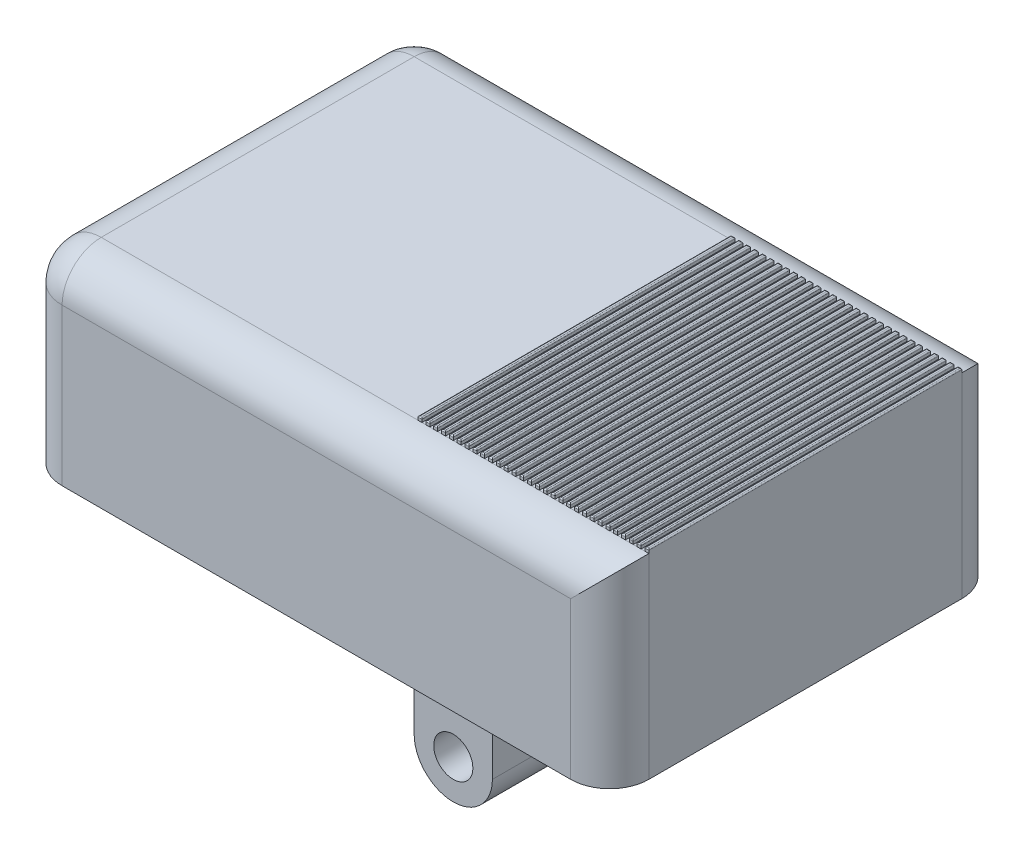
SolidWorks part; units mm, degrees
ref_plane "Front Plane" through (0, 0, 0) normal (0, 0, 1) x (1, 0, 0)
ref_plane "Top Plane" through (0, 0, 0) normal (0, 1, 0) x (1, 0, 0)
ref_plane "Right Plane" through (0, 0, 0) normal (1, 0, 0) x (0, 0, -1)
sketch "Sketch2" plane through (0, 0, 0) normal (0, 1, 0) x (1, 0, 0)
  line L1 (-37.5, -25) -> (37.5, -25)
  line L2 (-37.5, -25) -> (-37.5, 25)
  line L3 (-37.5, 25) -> (37.5, 25)
  line L4 (37.5, -25) -> (37.5, 25)
  line L5 (-37.5, -25) -> (37.5, 25) construction
  line L6 (-37.5, 25) -> (37.5, -25) construction
  point P0 (0, 0)
  dimension "D1" = 75
  dimension "D2" = 50
extrude "Boss-Extrude1" add sketch "Sketch2" along normal blind 25
sketch "Sketch3" plane through (0, 0, 0) normal (0, -1, 0) x (1, 0, 0)
  line L0 (37.5, 25) -> (37.5, -25) construction
  line L1 (7.5, -10) -> (17.5, -10)
  line L2 (7.5, -10) -> (7.5, 10)
  line L3 (7.5, 10) -> (17.5, 10)
  line L4 (17.5, -10) -> (17.5, 10)
  line L5 (7.5, -10) -> (17.5, 10) construction
  line L6 (7.5, 10) -> (17.5, -10) construction
  line L8 (7.5, 10) -> (17.5, 10)
  line L9 (7.5, 10) -> (7.5, 20)
  line L10 (7.5, 20) -> (17.5, 20)
  line L11 (17.5, 10) -> (17.5, 20)
  line L12 (7.5, -10) -> (17.5, -10)
  line L13 (7.5, -10) -> (7.5, -20)
  line L14 (7.5, -20) -> (17.5, -20)
  line L15 (17.5, -10) -> (17.5, -20)
  point P0 (12.5, 0)
  dimension "D1" = 20
  dimension "D2" = 20
  dimension "D3" = 10
  dimension "D4" = 10
  dimension "D5" = 10
extrude "Boss-Extrude2" add sketch "Sketch3" along normal blind 15 contours L15 L1 L13 L14 | L3 L11 L10 L9 region at (12.5, 0, -15) region at (12.5, 0, 15)
fillet "Fillet1" radius 5 4 edges at (17.5, -15, -15) (7.5, -15, -15) (17.5, -15, 15) (7.5, -15, 15)
sketch "Sketch4" plane through (0, 0, 20) normal (0, 0, 1) x (1, 0, 0)
  circle A0 centre (12.5, -10) radius 2.5
  dimension "D1" = 5
extrude "Cut-Extrude1" cut sketch "Sketch4" against normal through all
sketch "Sketch5" plane through (0, 0, 0) normal (0, -1, 0) x (1, 0, 0)
  line L0 (37.5, 25) -> (37.5, -25) construction
  circle A0 centre (27.5, 0) radius 2.75
  point P4 (0, 0)
  dimension "D1" = 5.5
  dimension "D2" = 10
extrude "Cut-Extrude2" cut sketch "Sketch5" against normal blind 5
sketch "Sketch6" plane through (0, 5, 0) normal (0, -1, 0) x (1, 0, 0)
  circle A0 centre (27.5, 0) radius 2.125
  dimension "D1" = 4.25
extrude "Boss-Extrude3" add sketch "Sketch6" along normal blind 10
ref_plane "Plane1" through (0, 2, 0) normal (0, -1, 0) x (-1, 0, 0)
sketch "Sketch7" plane through (0, 2, 0) normal (0, -1, 0) x (-1, 0, 0)
  line L0 (-27.5, 0) -> (-30.5, 0) construction
  line L1 (-27.5, 0) -> (-30.0981, -1.5)
  line L2 (-27.5, 0) -> (-30.0981, 1.5)
  line L3 (-27.5, 2.25) -> (-27.5, -2.25) construction
  line L4 (-27.5, 0) -> (-24.9019, 1.5)
  line L5 (-27.5, 0) -> (-24.9019, -1.5)
  circle A0 centre (-27.5, 0) radius 2.25
  circle A1 centre (-27.5, 0) radius 2.75
  point P11 (-27.5, 0)
  dimension "D1" = 4.5
  dimension "D7" = 5.5
  dimension "D2" = 3
  dimension "D3" = 3
  dimension "D4" = 3
  dimension "D5" = 30
  dimension "D6" = 30
extrude "Boss-Extrude4" add sketch "Sketch7" along normal blind 0.75 contours L2 A1 L1 A0 | L5 A1 L4 A0 region at (29.8953, 2, 0) region at (25.1047, 2, 0)
fillet "Fillet2" radius 5 7 edges at (-37.5, 12.5, -25) (0, 25, 25) (-37.5, 25, 0) (0, 25, -25) (37.5, 12.5, -25) (37.5, 12.5, 25) (-37.5, 12.5, 25)
sketch "Sketch8" plane through (0, 25, 0) normal (0, 1, 0) x (1, 0, 0)
  line L0 (37.5, 20) -> (-32.5, 20) construction
  line L1 (37.5, -20) -> (37, -20)
  line L2 (37.5, -20) -> (37.5, 20)
  line L3 (37.5, 20) -> (37, 20)
  line L4 (37, -20) -> (37, 20)
  line L5 (36.5, -20) -> (36.5, 20)
  line L6 (36.5, 20) -> (36, 20)
  line L7 (36, -20) -> (36, 20)
  line L8 (36.5, -20) -> (36, -20)
  line L9 (35.5, -20) -> (35.5, 20)
  line L10 (35.5, 20) -> (35, 20)
  line L11 (35, -20) -> (35, 20)
  line L12 (35.5, -20) -> (35, -20)
  line L13 (34.5, -20) -> (34.5, 20)
  line L14 (34.5, 20) -> (34, 20)
  line L15 (34, -20) -> (34, 20)
  line L16 (34.5, -20) -> (34, -20)
  line L17 (33.5, -20) -> (33.5, 20)
  line L18 (33.5, 20) -> (33, 20)
  line L19 (33, -20) -> (33, 20)
  line L20 (33.5, -20) -> (33, -20)
  line L21 (32.5, -20) -> (32.5, 20)
  line L22 (32.5, 20) -> (32, 20)
  line L23 (32, -20) -> (32, 20)
  line L24 (32.5, -20) -> (32, -20)
  line L25 (31.5, -20) -> (31.5, 20)
  line L26 (31.5, 20) -> (31, 20)
  line L27 (31, -20) -> (31, 20)
  line L28 (31.5, -20) -> (31, -20)
  line L29 (30.5, -20) -> (30.5, 20)
  line L30 (30.5, 20) -> (30, 20)
  line L31 (30, -20) -> (30, 20)
  line L32 (30.5, -20) -> (30, -20)
  line L33 (29.5, -20) -> (29.5, 20)
  line L34 (29.5, 20) -> (29, 20)
  line L35 (29, -20) -> (29, 20)
  line L36 (29.5, -20) -> (29, -20)
  line L37 (28.5, -20) -> (28.5, 20)
  line L38 (28.5, 20) -> (28, 20)
  line L39 (28, -20) -> (28, 20)
  line L40 (28.5, -20) -> (28, -20)
  line L41 (27.5, -20) -> (27.5, 20)
  line L42 (27.5, 20) -> (27, 20)
  line L43 (27, -20) -> (27, 20)
  line L44 (27.5, -20) -> (27, -20)
  line L45 (26.5, -20) -> (26.5, 20)
  line L46 (26.5, 20) -> (26, 20)
  line L47 (26, -20) -> (26, 20)
  line L48 (26.5, -20) -> (26, -20)
  line L49 (25.5, -20) -> (25.5, 20)
  line L50 (25.5, 20) -> (25, 20)
  line L51 (25, -20) -> (25, 20)
  line L52 (25.5, -20) -> (25, -20)
  line L53 (24.5, -20) -> (24.5, 20)
  line L54 (24.5, 20) -> (24, 20)
  line L55 (24, -20) -> (24, 20)
  line L56 (24.5, -20) -> (24, -20)
  line L57 (23.5, -20) -> (23.5, 20)
  line L58 (23.5, 20) -> (23, 20)
  line L59 (23, -20) -> (23, 20)
  line L60 (23.5, -20) -> (23, -20)
  line L61 (22.5, -20) -> (22.5, 20)
  line L62 (22.5, 20) -> (22, 20)
  line L63 (22, -20) -> (22, 20)
  line L64 (22.5, -20) -> (22, -20)
  line L65 (21.5, -20) -> (21.5, 20)
  line L66 (21.5, 20) -> (21, 20)
  line L67 (21, -20) -> (21, 20)
  line L68 (21.5, -20) -> (21, -20)
  line L69 (20.5, -20) -> (20.5, 20)
  line L70 (20.5, 20) -> (20, 20)
  line L71 (20, -20) -> (20, 20)
  line L72 (20.5, -20) -> (20, -20)
  line L73 (19.5, -20) -> (19.5, 20)
  line L74 (19.5, 20) -> (19, 20)
  line L75 (19, -20) -> (19, 20)
  line L76 (19.5, -20) -> (19, -20)
  line L77 (18.5, -20) -> (18.5, 20)
  line L78 (18.5, 20) -> (18, 20)
  line L79 (18, -20) -> (18, 20)
  line L80 (18.5, -20) -> (18, -20)
  line L81 (17.5, -20) -> (17.5, 20)
  line L82 (17.5, 20) -> (17, 20)
  line L83 (17, -20) -> (17, 20)
  line L84 (17.5, -20) -> (17, -20)
  line L85 (16.5, -20) -> (16.5, 20)
  line L86 (16.5, 20) -> (16, 20)
  line L87 (16, -20) -> (16, 20)
  line L88 (16.5, -20) -> (16, -20)
  line L89 (15.5, -20) -> (15.5, 20)
  line L90 (15.5, 20) -> (15, 20)
  line L91 (15, -20) -> (15, 20)
  line L92 (15.5, -20) -> (15, -20)
  line L93 (14.5, -20) -> (14.5, 20)
  line L94 (14.5, 20) -> (14, 20)
  line L95 (14, -20) -> (14, 20)
  line L96 (14.5, -20) -> (14, -20)
  line L97 (13.5, -20) -> (13.5, 20)
  line L98 (13.5, 20) -> (13, 20)
  line L99 (13, -20) -> (13, 20)
  line L100 (13.5, -20) -> (13, -20)
  line L101 (12.5, -20) -> (12.5, 20)
  line L102 (12.5, 20) -> (12, 20)
  line L103 (12, -20) -> (12, 20)
  line L104 (12.5, -20) -> (12, -20)
  line L105 (11.5, -20) -> (11.5, 20)
  line L106 (11.5, 20) -> (11, 20)
  line L107 (11, -20) -> (11, 20)
  line L108 (11.5, -20) -> (11, -20)
  line L109 (10.5, -20) -> (10.5, 20)
  line L110 (10.5, 20) -> (10, 20)
  line L111 (10, -20) -> (10, 20)
  line L112 (10.5, -20) -> (10, -20)
  line L113 (9.5, -20) -> (9.5, 20)
  line L114 (9.5, 20) -> (9, 20)
  line L115 (9, -20) -> (9, 20)
  line L116 (9.5, -20) -> (9, -20)
  line L117 (8.5, -20) -> (8.5, 20)
  line L118 (8.5, 20) -> (8, 20)
  line L119 (8, -20) -> (8, 20)
  line L120 (8.5, -20) -> (8, -20)
  line L121 (37.5, -20) -> (36.5, -20) construction
  dimension "D1" = 0.5
  dimension "D3" = 1
  dimension "D2" = 30
extrude "Boss-Extrude5" add sketch "Sketch8" along normal blind 0.5
fillet "Fillet3" radius 0.15 120 edges at (37.25, 25.5, 20) (37, 25.5, 0) (37.25, 25.5, -20) (37.5, 25.5, 0) (36, 25.5, 0) (36.25, 25.5, -20) (36.5, 25.5, 0) (36.25, 25.5, 20) (35, 25.5, 0) (35.25, 25.5, -20) (35.5, 25.5, 0) (35.25, 25.5, 20) (34, 25.5, 0) (34.25, 25.5, -20) (34.5, 25.5, 0) (34.25, 25.5, 20) (33, 25.5, 0) (33.25, 25.5, -20) (33.5, 25.5, 0) (33.25, 25.5, 20) (32, 25.5, 0) (32.25, 25.5, -20) (32.5, 25.5, 0) (32.25, 25.5, 20) (30, 25.5, 0) (30.25, 25.5, -20) (30.5, 25.5, 0) (30.25, 25.5, 20) (31, 25.5, 0) (31.25, 25.5, -20) (31.5, 25.5, 0) (31.25, 25.5, 20) (29, 25.5, 0) (29.25, 25.5, -20) (29.5, 25.5, 0) (29.25, 25.5, 20) (28, 25.5, 0) (28.25, 25.5, -20) (28.5, 25.5, 0) (28.25, 25.5, 20) (27, 25.5, 0) (27.25, 25.5, -20) (27.5, 25.5, 0) (27.25, 25.5, 20) (26, 25.5, 0) (26.25, 25.5, -20) (26.5, 25.5, 0) (26.25, 25.5, 20) (25, 25.5, 0) (25.25, 25.5, -20) (25.5, 25.5, 0) (25.25, 25.5, 20) (24, 25.5, 0) (24.25, 25.5, -20) (24.5, 25.5, 0) (24.25, 25.5, 20) (23, 25.5, 0) (23.25, 25.5, -20) (23.5, 25.5, 0) (23.25, 25.5, 20) (22, 25.5, 0) (22.25, 25.5, -20) (22.5, 25.5, 0) (22.25, 25.5, 20) (21, 25.5, 0) (21.25, 25.5, -20) (21.5, 25.5, 0) (21.25, 25.5, 20) (20, 25.5, 0) (20.25, 25.5, -20) (20.5, 25.5, 0) (20.25, 25.5, 20) (19, 25.5, 0) (19.25, 25.5, -20) (19.5, 25.5, 0) (19.25, 25.5, 20) (18, 25.5, 0) (18.25, 25.5, -20) (18.5, 25.5, 0) (18.25, 25.5, 20) (17, 25.5, 0) (17.25, 25.5, -20) (17.5, 25.5, 0) (17.25, 25.5, 20) (16, 25.5, 0) (16.25, 25.5, -20) (16.5, 25.5, 0) (16.25, 25.5, 20) (15, 25.5, 0) (15.25, 25.5, -20) (15.5, 25.5, 0) (15.25, 25.5, 20) (14, 25.5, 0) (14.25, 25.5, -20) (14.5, 25.5, 0) (14.25, 25.5, 20) (13, 25.5, 0) (13.25, 25.5, -20) (13.5, 25.5, 0) (13.25, 25.5, 20) (12, 25.5, 0) (12.25, 25.5, -20) (12.5, 25.5, 0) (12.25, 25.5, 20) (11, 25.5, 0) (11.25, 25.5, -20) (11.5, 25.5, 0) (11.25, 25.5, 20) (10, 25.5, 0) (10.25, 25.5, -20) (10.5, 25.5, 0) (10.25, 25.5, 20) (9, 25.5, 0) (9.25, 25.5, -20) (9.5, 25.5, 0) (9.25, 25.5, 20) (8, 25.5, 0) (8.25, 25.5, -20) (8.5, 25.5, 0) (8.25, 25.5, 20)
sketch "Sketch9" plane through (0, 0, 0) normal (0, -1, 0) x (1, 0, 0)
  line L0 (-37.5, -20) -> (-37.5, 20) construction
  line L1 (-25.5, -7.5) -> (-20.5, -7.5)
  line L2 (-25.5, -7.5) -> (-25.5, 7.5)
  line L3 (-25.5, 7.5) -> (-20.5, 7.5)
  line L4 (-20.5, -7.5) -> (-20.5, 7.5)
  line L5 (-25.5, -7.5) -> (-20.5, 7.5) construction
  line L6 (-25.5, 7.5) -> (-20.5, -7.5) construction
  point P0 (-23, 0)
  point P5 (0, 0)
  dimension "D1" = 12
  dimension "D2" = 5
  dimension "D3" = 15
extrude "Boss-Extrude6" add sketch "Sketch9" along normal blind 8
fillet "Fillet4" radius 2 6 edges at (-20.5, -4, 7.5) (-25.5, -4, 7.5) (-20.5, -4, -7.5) (-25.5, -4, -7.5) (-23, -8, -7.5) (-23, -8, 7.5)
sketch "Sketch10" plane through (-25.5, 0, 0) normal (-1, 0, 0) x (0, 0, 1)
  line L0 (5.5, -8) -> (-5.5, -8) construction
  circle A0 centre (0, -8) radius 4
  dimension "D1" = 8
extrude "Cut-Extrude3" cut sketch "Sketch10" against normal blind 10
fillet "Fillet5" radius 2 2 edges at (-23, -8, 4) (-23, -8, -4)
